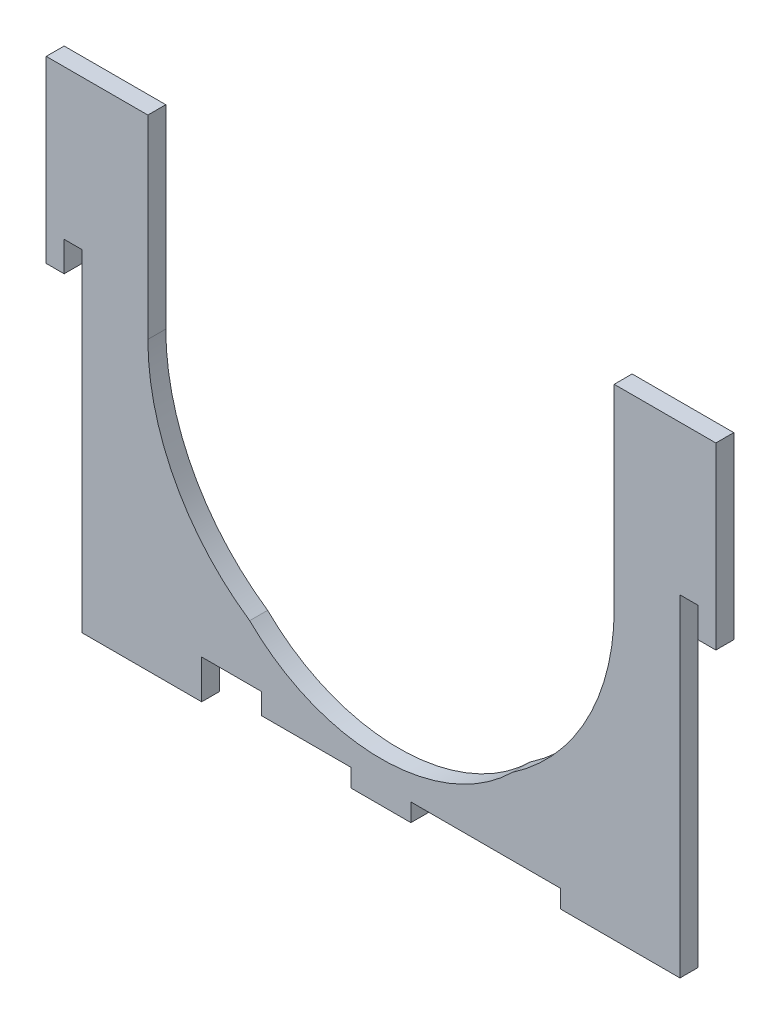
SolidWorks part; units mm, degrees
ref_plane "Front" through (0, 0, 0) normal (0, 0, 1) x (1, 0, 0)
ref_plane "Top" through (0, 0, 0) normal (0, 1, 0) x (1, 0, 0)
ref_plane "Right" through (0, 0, 0) normal (1, 0, 0) x (0, 0, -1)
sketch "Sketch1" plane through (0, 0, 0) normal (0, 0, 1) x (1, 0, 0)
  line L0 (-178, 90) -> (-178, 155)
  line L1 (0, 0) -> (-200, 0)
  line L2 (0, 0) -> (0, 155)
  line L3 (0, 155) -> (-22, 155)
  line L4 (-200, 0) -> (-200, 155)
  line L5 (-100, 155) -> (-100, 70) construction
  line L6 (-22, 90) -> (-22, 155)
  line L7 (-178, 155) -> (-200, 155)
  line L8 (-178, 155) -> (-22, 155) construction
  arc A0 (-178, 90) -> (-143.9432, 25.5563) centre (-100, 90) ccw
  arc A1 (-143.9432, 25.5563) -> (-56.0568, 25.5562) centre (-100, 70) ccw
  arc A2 (-56.0568, 25.5562) -> (-22, 90) centre (-100, 90) ccw
  dimension "D3" = 156
  dimension "D4" = 125
  dimension "D1" = 155
  dimension "D2" = 200
  dimension "D5" = 20
  dimension "D6" = 90
extrude "Boss-Extrude1" add sketch "Sketch1" along normal blind 6
sketch "Sketch3" plane through (0, 0, 6) normal (0, 0, 1) x (1, 0, 0)
  line L2 (-200, 155) -> (-200, 105)
  line L3 (-200, 105) -> (-206, 105)
  line L5 (-200, 155) -> (-212, 155)
  line L6 (-206, 105) -> (-206, 95)
  line L7 (-206, 95) -> (-212, 95)
  line L8 (-212, 155) -> (-212, 95)
  dimension "D1" = 50
  dimension "D2" = 6
  dimension "D3" = 12
  dimension "D4" = 10
extrude "Boss-Extrude2" add sketch "Sketch3" against normal blind 6
ref_plane "Plane1" through (-100, 0, 0) normal (-1, 0, 0) x (0, 0, 1)
mirror "Mirror1" about plane through (-100, 0, 0) normal (-1, 0, 0) of "Boss-Extrude2"
sketch "Sketch4" plane through (0, 0, 6) normal (0, 0, 1) x (1, 0, 0)
  line L0 (-200, 0) -> (0, 0) construction
  line L1 (-200, 0) -> (-160, 0)
  line L2 (-200, 0) -> (-200, -6)
  line L3 (-200, -6) -> (-160, -6)
  line L4 (-160, 0) -> (-160, -6)
  line L5 (-110, 0) -> (-90, 0)
  line L6 (-110, 0) -> (-110, -6)
  line L7 (-110, -6) -> (-90, -6)
  line L8 (-90, 0) -> (-90, -6)
  line L10 (0, 0) -> (-40, 0)
  line L11 (0, 0) -> (0, -6)
  line L12 (0, -6) -> (-40, -6)
  line L13 (-40, 0) -> (-40, -6)
  point P16 (-100, 0)
  point P17 (-100, 0)
  dimension "D1" = 6
  dimension "D2" = 40
  dimension "D3" = 20
extrude "Boss-Extrude3" add sketch "Sketch4" against normal blind 6
sketch "Sketch5" plane through (0, 0, 6) normal (0, 0, 1) x (1, 0, 0)
  line L1 (-160, 0) -> (-140, 0)
  line L2 (-160, 0) -> (-160, 7)
  line L3 (-160, 7) -> (-140, 7)
  line L4 (-140, 0) -> (-140, 7)
  dimension "D1" = 7
  dimension "D2" = 20
extrude "Cut-Extrude1" cut sketch "Sketch5" against normal blind 10
